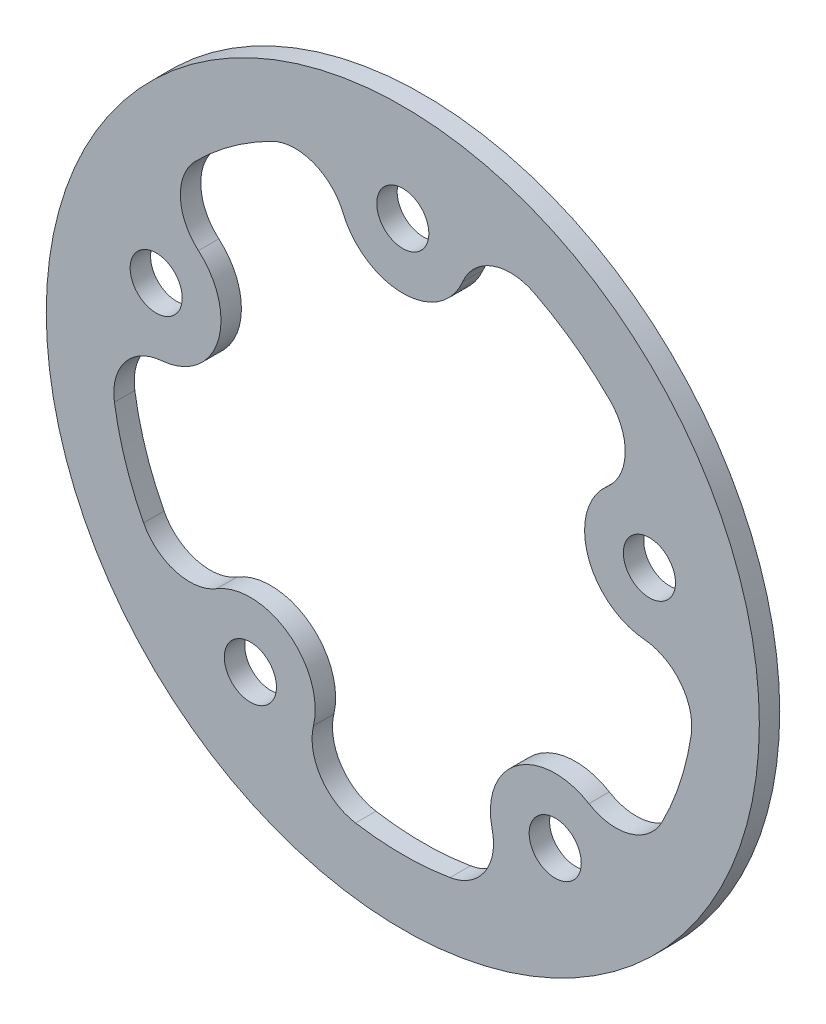
SolidWorks part; units mm, degrees
ref_plane "Front Plane" through (0, 0, 0) normal (0, 0, 1) x (1, 0, 0)
ref_plane "Top Plane" through (0, 0, 0) normal (0, 1, 0) x (1, 0, 0)
ref_plane "Right Plane" through (0, 0, 0) normal (1, 0, 0) x (0, 0, -1)
sketch "Sketch1" plane through (0, 0, 0) normal (0, 0, 1) x (1, 0, 0)
  line L0 (0, 25.4) -> (0, 0) construction
  line L1 (0, -28.575) -> (0, -34.925) construction
  circle A0 centre (0, 0) radius 34.925
  circle A1 centre (0, 25.4) radius 2.5527
  arc A2 (5.8594, 22.9526) -> (-5.8594, 22.9526) centre (0, 25.4) cw
  arc A3 (-28.2482, -4.3091) -> (-25.3861, -13.1178) centre (0, 0) ccw
  arc A4 (5.8594, 22.9526) -> (12.8274, 25.5341) centre (10.5469, 20.9947) cw
  arc A5 (-5.8594, 22.9526) -> (-12.8274, 25.5341) centre (-10.5469, 20.9947) ccw
  arc A6 (23.6399, 1.5201) -> (20.0186, 12.6654) centre (24.1568, 7.849) cw
  circle A7 centre (24.1568, 7.849) radius 2.5527
  arc A8 (20.0186, 12.6654) -> (20.3205, 20.09) centre (16.7079, 16.5185) ccw
  arc A9 (23.6399, 1.5201) -> (28.2482, -4.3091) centre (23.2263, -3.543) cw
  arc A10 (8.7508, -22.0131) -> (18.2316, -15.125) centre (14.9297, -20.549) cw
  circle A11 centre (14.9297, -20.549) radius 2.5527
  arc A12 (18.2316, -15.125) -> (25.3861, -13.1178) centre (20.873, -10.7857) ccw
  arc A13 (8.7508, -22.0131) -> (4.631, -28.1972) centre (3.8077, -23.1844) cw
  arc A14 (-18.2316, -15.125) -> (-8.7508, -22.0131) centre (-14.9297, -20.549) cw
  circle A15 centre (-14.9297, -20.549) radius 2.5527
  arc A16 (-8.7508, -22.0131) -> (-4.631, -28.1972) centre (-3.8077, -23.1844) ccw
  arc A17 (-18.2316, -15.125) -> (-25.3861, -13.1178) centre (-20.873, -10.7857) cw
  arc A18 (-20.0186, 12.6654) -> (-23.6399, 1.5201) centre (-24.1568, 7.849) cw
  circle A19 centre (-24.1568, 7.849) radius 2.5527
  arc A20 (-23.6399, 1.5201) -> (-28.2482, -4.3091) centre (-23.2263, -3.543) ccw
  arc A21 (-20.0186, 12.6654) -> (-20.3205, 20.09) centre (-16.7079, 16.5185) cw
  arc A22 (-4.631, -28.1972) -> (4.631, -28.1972) centre (0, 0) ccw
  arc A23 (25.3861, -13.1178) -> (28.2482, -4.3091) centre (0, 0) ccw
  arc A24 (20.3205, 20.09) -> (12.8274, 25.5341) centre (0, 0) ccw
  arc A25 (-12.8274, 25.5341) -> (-20.3205, 20.09) centre (0, 0) ccw
  point P9 (24.3143, 7.9002)
  dimension "D1" = 69.85
  dimension "D2" = 5.1054
  dimension "D4" = 5.08
  dimension "D5" = 6.35
  dimension "D6" = 25.4
  dimension "D3" = 6.35
  dimension "D7" = 5
extrude "Boss-Extrude1" add sketch "Sketch1" along normal blind 2
